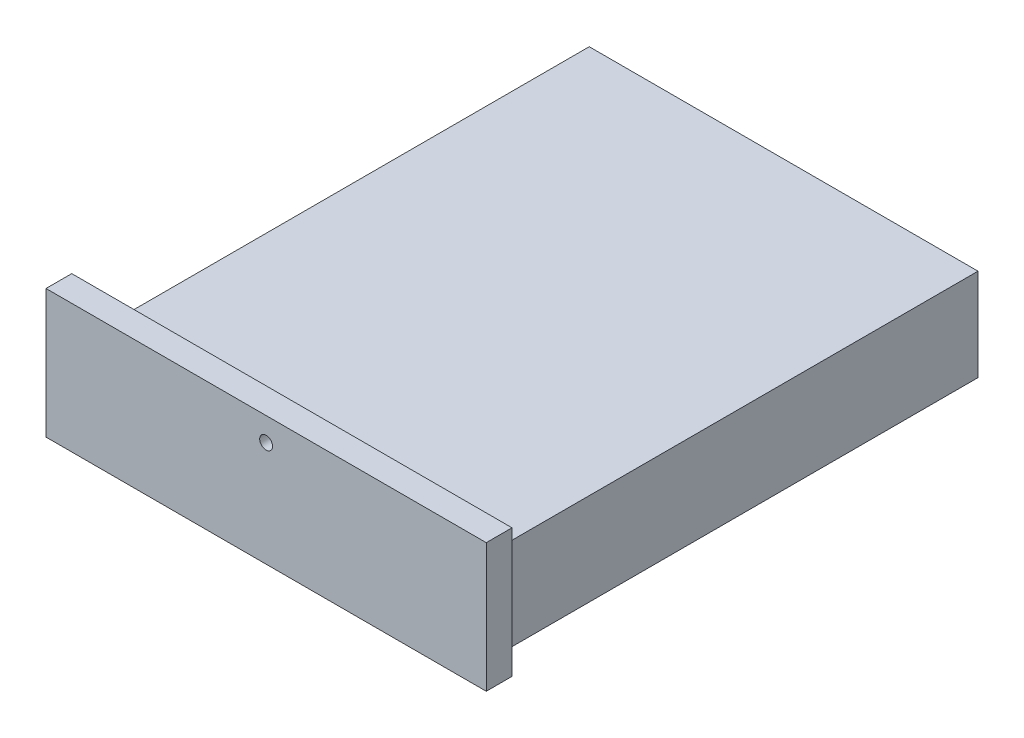
SolidWorks part; units mm, degrees
ref_plane "Front Plane" through (0, 0, 0) normal (0, 0, 1) x (1, 0, 0)
ref_plane "Top Plane" through (0, 0, 0) normal (0, 1, 0) x (1, 0, 0)
ref_plane "Right Plane" through (0, 0, 0) normal (1, 0, 0) x (0, 0, -1)
sketch "Sketch1" plane through (0, -22.4385, -0.0002) normal (0, 1, 0) x (1, 0, 0)
  line L4 (131.338, 7.003) -> (129.338, 7.003)
  line L5 (131.338, 7.003) -> (129.338, 7.003)
  line L6 (78.038, 7.003) -> (78.038, 26.103)
  line L7 (78.038, 7.003) -> (78.038, 26.103)
  line L14 (78.038, 26.103) -> (62.938, 26.103)
  line L15 (78.038, 26.103) -> (62.938, 26.103)
  line L16 (62.938, 26.103) -> (62.938, 6.103)
  line L17 (62.938, 26.103) -> (62.938, 6.103)
  line L26 (146.4404, 26.103) -> (131.338, 26.103)
  line L27 (146.4404, 26.103) -> (131.338, 26.103)
  line L28 (131.338, 26.103) -> (131.338, 7.003)
  line L29 (131.338, 26.103) -> (131.338, 7.003)
  line L75 (114.238, 7.003) -> (112.238, 7.003)
  line L76 (114.238, 7.003) -> (112.238, 7.003)
  line L77 (129.338, 7.003) -> (129.338, 26.103)
  line L78 (129.338, 7.003) -> (129.338, 26.103)
  line L79 (62.938, 6.103) -> (60.5428, 6.103)
  line L80 (62.938, 6.103) -> (60.5428, 6.103)
  line L81 (146.4404, 6.103) -> (146.4404, 26.103)
  line L82 (146.4404, 6.103) -> (146.4404, 26.103)
  line L83 (129.338, 26.103) -> (114.238, 26.103)
  line L84 (129.338, 26.103) -> (114.238, 26.103)
  line L85 (114.238, 26.103) -> (114.238, 7.003)
  line L86 (114.238, 26.103) -> (114.238, 7.003)
  line L87 (97.138, 7.003) -> (95.138, 7.003)
  line L88 (97.138, 7.003) -> (95.138, 7.003)
  line L89 (112.238, 7.003) -> (112.238, 26.103)
  line L90 (112.238, 7.003) -> (112.238, 26.103)
  line L91 (112.238, 26.103) -> (97.138, 26.103)
  line L92 (112.238, 26.103) -> (97.138, 26.103)
  line L93 (97.138, 26.103) -> (97.138, 7.003)
  line L94 (97.138, 26.103) -> (97.138, 7.003)
  line L95 (80.038, 7.003) -> (78.038, 7.003)
  line L96 (80.038, 7.003) -> (78.038, 7.003)
  line L97 (95.138, 7.003) -> (95.138, 26.103)
  line L98 (95.138, 7.003) -> (95.138, 26.103)
  line L99 (95.138, 26.103) -> (80.038, 26.103)
  line L100 (95.138, 26.103) -> (80.038, 26.103)
  line L101 (80.038, 26.103) -> (80.038, 7.003)
  line L102 (80.038, 26.103) -> (80.038, 7.003)
  line L111 (149.0321, 6.103) -> (146.4404, 6.103)
  line L112 (149.0321, 6.103) -> (146.4404, 6.103)
  arc A1 (60.5428, 6.103) -> (60.5959, 6.0115) centre (73.6219, 13.6322) ccw
  arc A2 (60.5428, 6.103) -> (60.5959, 6.0115) centre (73.6219, 13.6322) ccw
  spline S3 degree 3 poles (1817.8665, 957.8692) (-1812.7007, -801.1687) (1972.7377, 742.4675) (-1779.9076, -773.9188) knots -29.662381 -29.662381 -29.662381 -29.662381 32.998383 32.998383 32.998383 32.998383 only from (61.1644, 5.1151) to (62.5644, 3.3076)
  spline S4 degree 3 poles (548.8295, -1936.4915) (68.1721, 117.1489) (41.7438, 23.7507) (63.9834, 1.8165) (64.3645, 1.4758) (65.5511, 0.508) (66.3975, -0.0681) (68.1618, -1.131) (69.0656, -1.6129) (70.9072, -2.4757) (71.8473, -2.8546) (73.758, -3.5302) (74.728, -3.8283) (76.6807, -4.3902) (77.6629, -4.6553) (79.6355, -5.163) (80.6269, -5.4019) (82.6154, -5.8388) (83.6137, -6.0359) (85.6141, -6.4083) (86.6163, -6.584) (88.622, -6.928) (89.6256, -7.0959) (92.6392, -7.5851) (94.6533, -7.8906) (97.6787, -8.2804) (98.6882, -8.3974) (100.712, -8.5681) (101.7263, -8.6231) (103.759, -8.6779) (104.7772, -8.6815) (106.8164, -8.6518) (107.8346, -8.6197) (109.8636, -8.4895) (110.8742, -8.3881) (112.8914, -8.1479) (113.898, -8.0094) (116.9153, -7.5695) (118.9237, -7.2381) (121.9279, -6.7189) (122.9282, -6.542) (124.9259, -6.1777) (125.9229, -5.9891) (127.9067, -5.5749) (128.8931, -5.3485) (130.8559, -4.8592) (131.8333, -4.6003) (133.7815, -4.0591) (134.7528, -3.7785) (136.6775, -3.1531) (137.6304, -2.8065) (139.0374, -2.2069) (139.5031, -1.9951) (140.4295, -1.554) (140.891, -1.3271) (141.8041, -0.8385) (142.2585, -0.5733) (143.1225, 0.0059) (143.536, 0.3177) (144.1477, 0.7954) (144.3502, 0.9564) (144.7554, 1.2781) (144.9578, 1.4391) (162.9576, 16.0958) (166.0883, 48.1369) (-1083.6442, 1578.9651) knots -0.820445 -0.820445 -0.820445 -0.820445 0.115071 0.115071 0.130696 0.130696 0.161946 0.161946 0.193196 0.193196 0.224446 0.224446 0.255696 0.255696 0.286946 0.286946 0.318196 0.318196 0.349446 0.349446 0.380696 0.380696 0.411946 0.411946 0.474446 0.474446 0.505696 0.505696 0.536946 0.536946 0.568196 0.568196 0.599446 0.599446 0.630696 0.630696 0.661946 0.661946 0.724446 0.724446 0.755696 0.755696 0.786946 0.786946 0.818196 0.818196 0.849446 0.849446 0.880696 0.880696 0.911946 0.911946 0.927571 0.927571 0.943196 0.943196 0.958821 0.958821 0.974446 0.974446 0.982259 0.982259 0.990071 0.990071 1.683487 1.683487 1.683487 1.683487 only from (62.5644, 3.3076) to (145.9103, 2.2401)
  spline S6 degree 3 poles (61.1644, 5.1151) (61.5972, 4.4806) (62.0704, 3.8809) (62.5644, 3.3076) knots 0 0 0 0 0.685452 0.685452 0.685452 0.685452 construction
  spline S7 degree 3 poles (62.5644, 3.3076) (62.9009, 2.9175) (63.2527, 2.5372) (63.9834, 1.8165) (64.3645, 1.4758) (65.5511, 0.508) (66.3975, -0.0681) (68.1618, -1.131) (69.0656, -1.6129) (70.9072, -2.4757) (71.8473, -2.8546) (73.758, -3.5302) (74.728, -3.8283) (76.6807, -4.3902) (77.6629, -4.6553) (79.6355, -5.163) (80.6269, -5.4019) (82.6154, -5.8388) (83.6137, -6.0359) (85.6141, -6.4083) (86.6163, -6.584) (88.622, -6.928) (89.6256, -7.0959) (92.6392, -7.5851) (94.6533, -7.8906) (97.6787, -8.2804) (98.6882, -8.3974) (100.712, -8.5681) (101.7263, -8.6231) (103.759, -8.6779) (104.7772, -8.6815) (106.8164, -8.6518) (107.8346, -8.6197) (109.8636, -8.4895) (110.8742, -8.3881) (112.8914, -8.1479) (113.898, -8.0094) (116.9153, -7.5695) (118.9237, -7.2381) (121.9279, -6.7189) (122.9282, -6.542) (124.9259, -6.1777) (125.9229, -5.9891) (127.9067, -5.5749) (128.8931, -5.3485) (130.8559, -4.8592) (131.8333, -4.6003) (133.7815, -4.0591) (134.7528, -3.7785) (136.6775, -3.1531) (137.6304, -2.8065) (139.0374, -2.2069) (139.5031, -1.9951) (140.4295, -1.554) (140.891, -1.3271) (141.8041, -0.8385) (142.2585, -0.5733) (143.1225, 0.0059) (143.536, 0.3177) (144.1477, 0.7954) (144.3502, 0.9564) (144.7554, 1.2781) (144.9578, 1.4391) (145.4132, 1.8099) (145.6651, 2.021) (145.9103, 2.2401) knots 0.099446 0.099446 0.099446 0.099446 0.115071 0.115071 0.130696 0.130696 0.161946 0.161946 0.193196 0.193196 0.224446 0.224446 0.255696 0.255696 0.286946 0.286946 0.318196 0.318196 0.349446 0.349446 0.380696 0.380696 0.411946 0.411946 0.474446 0.474446 0.505696 0.505696 0.536946 0.536946 0.568196 0.568196 0.599446 0.599446 0.630696 0.630696 0.661946 0.661946 0.724446 0.724446 0.755696 0.755696 0.786946 0.786946 0.818196 0.818196 0.849446 0.849446 0.880696 0.880696 0.911946 0.911946 0.927571 0.927571 0.943196 0.943196 0.958821 0.958821 0.974446 0.974446 0.982259 0.982259 0.990071 0.990071 1 1 1 1 construction
  spline S16 degree 3 poles (1372.6595, -1576.7465) (65.1848, 24.8122) (129.0525, -14.1517) (146.6971, 2.9872) (147.0468, 3.3764) (147.7131, 4.1895) (148.0276, 4.6072) (165.4719, 29.2726) (129.935, 85.2105) (-1517.3371, 1110.9512) knots -0.67008 -0.67008 -0.67008 -0.67008 0.055384 0.055384 0.071009 0.071009 0.086634 0.086634 0.976126 0.976126 0.976126 0.976126 only from (145.9103, 2.2401) to (149.0321, 6.103)
  spline S17 degree 3 poles (145.9103, 2.2401) (146.0509, 2.3658) (146.1894, 2.4941) (146.6971, 2.9872) (147.0468, 3.3764) (147.7131, 4.1895) (148.0276, 4.6072) (148.5757, 5.3822) (148.8117, 5.7379) (149.0321, 6.103) knots 0.049688 0.049688 0.049688 0.049688 0.055384 0.055384 0.071009 0.071009 0.086634 0.086634 0.099446 0.099446 0.099446 0.099446
  spline S46 degree 3 poles (1817.9148, 957.8926) (-1812.905, -801.2651) (1973.1102, 742.6193) (-1780.4367, -774.1326) knots -28.662659 -28.662659 -28.662659 -28.662659 34.001328 34.001328 34.001328 34.001328 only from (60.5959, 6.0115) to (61.1644, 5.1151)
  spline S47 degree 3 poles (60.5959, 6.0115) (60.7756, 5.7048) (60.9657, 5.4063) (61.1644, 5.1151) knots 0.685452 0.685452 0.685452 0.685452 1 1 1 1
  dimension "D1" = 0
sketch "Sketch3" plane through (0, 0.0002, -26.103) normal (0, 0, 1) x (1, 0, 0)
  line L1 (97.138, 49.3018) -> (112.238, 49.3018)
  line L2 (97.138, 49.3018) -> (97.138, 45.7197)
  line L3 (97.138, 45.7197) -> (112.238, 45.7197)
  line L4 (112.238, 49.3018) -> (112.238, 45.7197)
  line L6 (97.1381, 145.3715) -> (97.138, -22.4385) construction
  line L7 (112.2381, 145.3715) -> (112.238, -22.4385) construction
  dimension "D1" = 15.1
extrude "Boss-Extrude1" add sketch "Sketch3" along normal up to surface (19.1 mm away)
sketch "Sketch4" plane through (0, 0.0001, -7.003) normal (0, 0, 1) x (1, 0, 0)
  line L0 (95.138, -22.4385) -> (95.1381, 145.3715) construction
  line L1 (96.138, 50.7197) -> (113.238, 50.7197)
  line L2 (96.138, 50.7197) -> (96.138, 45.7197)
  line L3 (96.138, 45.7197) -> (113.238, 45.7197)
  line L4 (113.238, 50.7197) -> (113.238, 45.7197)
  line L5 (97.138, -22.4385) -> (97.1381, 145.3715) construction
  line L6 (95.138, 37.2586) -> (97.138, 37.2586) construction
  line L9 (96.138, 37.2586) -> (96.138, 50.3435) construction
  line L10 (112.238, 37.2586) -> (114.238, 37.2586) construction
  line L13 (113.238, 37.2586) -> (113.238, 50.5667) construction
  line L14 (112.238, -22.4385) -> (112.2381, 145.3715) construction
  line L15 (114.238, -22.4385) -> (114.2381, 145.3715) construction
  line L16 (112.238, 45.7197) -> (97.138, 45.7197) construction
  point P8 (95.138, 37.4026)
  point P11 (112.238, 37.2617)
  point P18 (114.238, 36.9082)
  point P22 (95.138, 37.5209)
  point P24 (113.238, 37.2586)
  point P25 (113.3512, 38.2942)
  point P26 (96.3821, 38.5174)
  point P27 (0, 0)
  dimension "D1" = 5
extrude "Boss-Extrude2" add sketch "Sketch4" along normal blind 1
sketch "Sketch6" plane through (0, 0, -6.003) normal (0, 0, 1) x (1, 0, 0)
  line L0 (96.138, 48.2197) -> (113.238, 48.2197) construction
  line L1 (96.138, 50.7197) -> (96.138, 45.7197) construction
  line L2 (113.238, 45.7197) -> (113.238, 50.7197) construction
  line L3 (104.688, 50.7197) -> (104.688, 45.7197) construction
  line L4 (113.238, 50.7197) -> (96.138, 50.7197) construction
  line L5 (96.138, 45.7197) -> (113.238, 45.7197) construction
  point P0 (104.688, 49.8079)
  point P13 (104.688, 49.8079)
  point P17 (104.688, 49.4697)
hole_wizard "Ø1.0mm Dowel Hole1" positions "Sketch7" profile "Sketch8" hole size "Ø1.0" standard "AS" end condition up to next
sketch "Sketch7" plane through (0, 0, -6.003) normal (0, 0, 1) x (1, 0, 0)
  point P0 (104.688, 49.8079)
sketch "Sketch8" plane through (104.688, 49.8079, -6.0026) normal (1, 0, 0) x (0, -1, 0)
  line L0 (0, 0) -> (0, 1)
  line L1 (0, 1) -> (0.25, 1)
  line L2 (0.25, 1) -> (0.25, 0)
  line L5 (0.25, 0) -> (0, 0)
  line L11 (0, -6.35) -> (0, 107.95) construction
  dimension "Thru Hole Dia." = 0.5
  dimension "Thru Hole Depth" = 1
